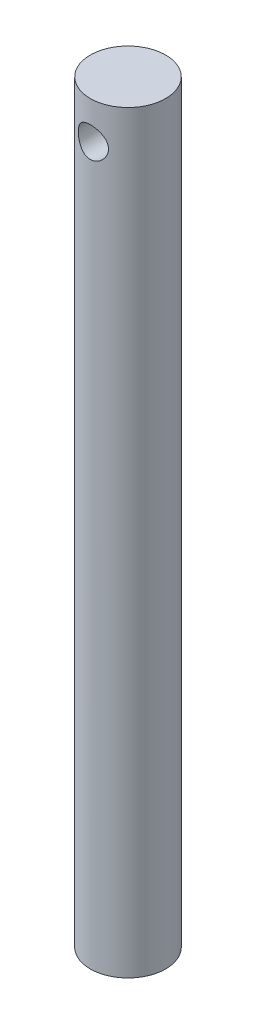
SolidWorks part; units mm, degrees
ref_plane "Front Plane" through (0, 0, 0) normal (0, 0, 1) x (1, 0, 0)
ref_plane "Top Plane" through (0, 0, 0) normal (0, 1, 0) x (1, 0, 0)
ref_plane "Right Plane" through (0, 0, 0) normal (1, 0, 0) x (0, 0, -1)
sketch "Sketch1" plane through (0, 0, 0) normal (0, 1, 0) x (1, 0, 0)
  circle A0 centre (0, 0) radius 15
  dimension "D1" = 30
extrude "Boss-Extrude1" add sketch "Sketch1" along normal blind 300
sketch "Sketch2" plane through (0, 0, 0) normal (0, 0, 1) x (1, 0, 0)
  line L0 (15, 300) -> (-15, 300) construction
  circle A0 centre (0, 285) radius 6
  point P5 (0, 0)
  dimension "D2" = 12
  dimension "D1" = 15
extrude "Cut-Extrude1" cut sketch "Sketch2" along normal through all both and the other way through all
